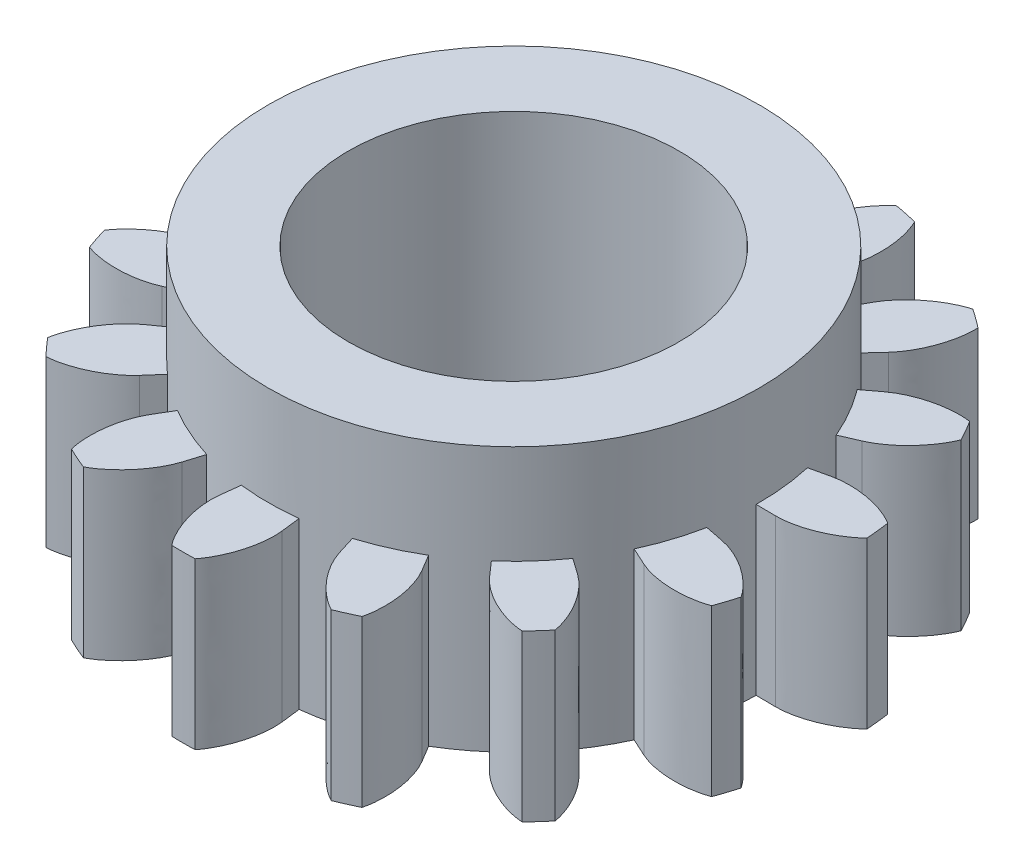
SolidWorks part; units mm, degrees
ref_plane "Front Plane" through (0, 0, 0) normal (0, 0, 1) x (1, 0, 0)
ref_plane "Top Plane" through (0, 0, 0) normal (0, 1, 0) x (1, 0, 0)
ref_plane "Right Plane" through (0, 0, 0) normal (1, 0, 0) x (0, 0, -1)
sketch "Sketch1" plane through (0, 0, 0) normal (0, 1, 0) x (1, 0, 0)
  line L0 (-8.7707, -0.0085) -> (8.7293, -0.0085) construction
  dimension "D1" = 17.5
sketch "Sketch2" plane through (0, 0, 0) normal (0, 1, 0) x (1, 0, 0)
  line L0 (-2.583, 7.5851) -> (-2.3919, 7.0239)
  line L1 (-0.7409, 7.9785) -> (-0.6861, 7.3882)
  line L2 (0, 0) -> (-2.6402, 12.3623) construction
  line L3 (2.5683, 7.5901) -> (2.3783, 7.0285)
  line L4 (0.7255, 7.9799) -> (0.6718, 7.3895)
  line L5 (5.4334, 5.8892) -> (5.0314, 5.4536)
  line L6 (3.9085, 6.9949) -> (3.6193, 6.4774)
  line L7 (7.359, 3.1701) -> (6.8146, 2.9356)
  line L8 (6.4157, 4.8005) -> (5.941, 4.4453)
  line L9 (8.0122, -0.0971) -> (7.4195, -0.0899)
  line L10 (7.8135, 1.776) -> (7.2355, 1.6446)
  line L11 (7.28, -3.3476) -> (6.7414, -3.0999)
  line L12 (7.8604, -1.5556) -> (7.2788, -1.4405)
  line L13 (5.289, -6.0192) -> (4.8977, -5.5739)
  line L14 (6.5481, -4.6182) -> (6.0636, -4.2766)
  line L15 (2.3835, -7.6501) -> (2.2072, -7.0841)
  line L16 (4.1036, -6.8823) -> (3.8, -6.3731)
  line L17 (-0.9341, -7.9582) -> (-0.865, -7.3694)
  line L18 (0.9495, -7.9564) -> (0.8793, -7.3677)
  line L19 (-4.0902, -6.8902) -> (-3.7876, -6.3805)
  line L20 (-2.3687, -7.6547) -> (-2.1935, -7.0884)
  line L21 (-6.5391, -4.6309) -> (-6.0553, -4.2883)
  line L22 (-5.2774, -6.0295) -> (-4.887, -5.5834)
  line L23 (-7.8573, -1.5708) -> (-7.276, -1.4546)
  line L24 (-7.2735, -3.3617) -> (-6.7354, -3.113)
  line L25 (-7.8169, 1.7608) -> (-7.2386, 1.6306)
  line L26 (-8.012, -0.1126) -> (-7.4193, -0.1043)
  line L27 (-6.4249, 4.788) -> (-5.9496, 4.4338)
  line L28 (-7.3652, 3.1559) -> (-6.8203, 2.9224)
  line L29 (-3.922, 6.9874) -> (-3.6318, 6.4704)
  line L30 (-5.4448, 5.8787) -> (-5.042, 5.4438)
  circle A0 centre (0, 0) radius 8.75 construction
  arc A1 (-1.7416, 9.8472) -> (-2.433, 9.6995) centre (0, 0) ccw
  circle A2 centre (0, 0) radius 7.42
  arc A3 (2.4142, 9.7042) -> (1.7225, 9.8505) centre (0, 0) ccw
  circle A4 centre (0, 0) radius 8.0128 construction
  arc A5 (6.1525, 7.8833) -> (5.5802, 8.2983) centre (0, 0) ccw
  arc A6 (8.827, 4.6993) -> (8.473, 5.3112) centre (0, 0) ccw
  arc A7 (9.9753, 0.7027) -> (9.9007, 1.4058) centre (0, 0) ccw
  arc A8 (9.3987, -3.4153) -> (9.6165, -2.7428) centre (0, 0) ccw
  arc A9 (7.197, -6.9429) -> (7.6695, -6.417) centre (0, 0) ccw
  arc A10 (3.7509, -9.2699) -> (4.3964, -8.9817) centre (0, 0) ccw
  arc A11 (-0.3438, -9.9941) -> (0.3632, -9.9934) centre (0, 0) ccw
  arc A12 (-4.3791, -8.9902) -> (-3.7329, -9.2771) centre (0, 0) ccw
  arc A13 (-7.6571, -6.4318) -> (-7.1835, -6.9568) centre (0, 0) ccw
  arc A14 (-9.6112, -2.7614) -> (-9.3921, -3.4335) centre (0, 0) ccw
  arc A15 (-9.9034, 1.3866) -> (-9.9766, 0.6834) centre (0, 0) ccw
  arc A16 (-8.4832, 5.2948) -> (-8.8361, 4.6822) centre (0, 0) ccw
  arc A17 (-5.5962, 8.2875) -> (-6.1678, 7.8714) centre (0, 0) ccw
  spline S0 degree 3 poles (-2.583, 7.5851) (-2.7933, 8.2026) (-2.7279, 9.0974) (-2.433, 9.6995) knots 0 0 0 0 1 1 1 1
  spline S1 degree 3 poles (-0.7409, 7.9785) (-0.8012, 8.6281) (-1.2264, 9.4181) (-1.7416, 9.8472) knots 0 0 0 0 1 1 1 1
  spline S2 degree 3 poles (2.5683, 7.5901) (2.7774, 8.208) (2.7103, 9.1027) (2.4142, 9.7042) knots 0 0 0 0 1 1 1 1
  spline S3 degree 3 poles (0.7255, 7.9799) (0.7845, 8.6296) (1.2082, 9.4205) (1.7225, 9.8505) knots 0 0 0 0 1 1 1 1
  spline S4 degree 3 poles (5.4334, 5.8892) (5.8758, 6.3687) (6.1784, 7.2134) (6.1525, 7.8833) knots 0 0 0 0 1 1 1 1
  spline S5 degree 3 poles (3.9085, 6.9949) (4.2267, 7.5644) (4.9354, 8.1146) (5.5802, 8.2983) knots 0 0 0 0 1 1 1 1
  spline S6 degree 3 poles (7.359, 3.1701) (7.9582, 3.4282) (8.5782, 4.0768) (8.827, 4.6993) knots 0 0 0 0 1 1 1 1
  spline S7 degree 3 poles (6.4157, 4.8005) (6.938, 5.1913) (7.8092, 5.4056) (8.473, 5.3112) knots 0 0 0 0 1 1 1 1
  spline S8 degree 3 poles (8.0122, -0.0971) (8.6646, -0.105) (9.4947, 0.2353) (9.9753, 0.7027) knots 0 0 0 0 1 1 1 1
  spline S9 degree 3 poles (7.8135, 1.776) (8.4497, 1.9206) (9.3327, 1.762) (9.9007, 1.4058) knots 0 0 0 0 1 1 1 1
  spline S10 degree 3 poles (7.28, -3.3476) (7.8727, -3.6202) (8.7695, -3.6469) (9.3987, -3.4153) knots 0 0 0 0 1 1 1 1
  spline S11 degree 3 poles (7.8604, -1.5556) (8.5003, -1.6823) (9.2426, -2.1863) (9.6165, -2.7428) knots 0 0 0 0 1 1 1 1
  spline S12 degree 3 poles (5.289, -6.0192) (5.7197, -6.5093) (6.528, -6.8985) (7.197, -6.9429) knots 0 0 0 0 1 1 1 1
  spline S13 degree 3 poles (6.5481, -4.6182) (7.0812, -4.9942) (7.5542, -5.7566) (7.6695, -6.417) knots 0 0 0 0 1 1 1 1
  spline S14 degree 3 poles (2.3835, -7.6501) (2.5776, -8.2729) (3.1578, -8.9573) (3.7509, -9.2699) knots 0 0 0 0 1 1 1 1
  spline S15 degree 3 poles (4.1036, -6.8823) (4.4377, -7.4426) (4.5597, -8.3315) (4.3964, -8.9817) knots 0 0 0 0 1 1 1 1
  spline S16 degree 3 poles (-0.9341, -7.9582) (-1.0102, -8.6061) (-0.7585, -9.4673) (-0.3438, -9.9941) knots 0 0 0 0 1 1 1 1
  spline S17 degree 3 poles (0.9495, -7.9564) (1.0268, -8.6041) (0.7768, -9.4658) (0.3632, -9.9934) knots 0 0 0 0 1 1 1 1
  spline S18 degree 3 poles (-4.0902, -6.8902) (-4.4232, -7.4512) (-4.5436, -8.3403) (-4.3791, -8.9902) knots 0 0 0 0 1 1 1 1
  spline S19 degree 3 poles (-2.3687, -7.6547) (-2.5616, -8.2779) (-3.1404, -8.9634) (-3.7329, -9.2771) knots 0 0 0 0 1 1 1 1
  spline S20 degree 3 poles (-6.5391, -4.6309) (-7.0715, -5.0079) (-7.5431, -5.7712) (-7.6571, -6.4318) knots 0 0 0 0 1 1 1 1
  spline S21 degree 3 poles (-5.2774, -6.0295) (-5.7071, -6.5204) (-6.5147, -6.9111) (-7.1835, -6.9568) knots 0 0 0 0 1 1 1 1
  spline S22 degree 3 poles (-7.8573, -1.5708) (-8.4971, -1.6987) (-9.2383, -2.2042) (-9.6112, -2.7614) knots 0 0 0 0 1 1 1 1
  spline S23 degree 3 poles (-7.2735, -3.3617) (-7.8657, -3.6354) (-8.7625, -3.6639) (-9.3921, -3.4335) knots 0 0 0 0 1 1 1 1
  spline S24 degree 3 poles (-7.8169, 1.7608) (-8.4534, 1.9042) (-9.3361, 1.7439) (-9.9034, 1.3866) knots 0 0 0 0 1 1 1 1
  spline S25 degree 3 poles (-8.012, -0.1126) (-8.6643, -0.1218) (-9.4951, 0.2169) (-9.9766, 0.6834) knots 0 0 0 0 1 1 1 1
  spline S26 degree 3 poles (-6.4249, 4.788) (-6.948, 5.1779) (-7.8197, 5.3905) (-8.4832, 5.2948) knots 0 0 0 0 1 1 1 1
  spline S27 degree 3 poles (-7.3652, 3.1559) (-7.9648, 3.4128) (-8.586, 4.0602) (-8.8361, 4.6822) knots 0 0 0 0 1 1 1 1
  spline S28 degree 3 poles (-3.922, 6.9874) (-4.2413, 7.5563) (-4.9511, 8.105) (-5.5962, 8.2875) knots 0 0 0 0 1 1 1 1
  spline S29 degree 3 poles (-5.4448, 5.8787) (-5.8881, 6.3574) (-6.1923, 7.2014) (-6.1678, 7.8714) knots 0 0 0 0 1 1 1 1
  point P129 (0, 0)
  dimension "D1" = 17.5
  dimension "D2" = 20
  dimension "D3" = 6.75
  dimension "D4" = 15
extrude "Boss-Extrude1" add sketch "Sketch2" along normal blind 5 contours A2 | S21 L22 A2 L21 S20 A13 | S19 L20 A2 L19 S18 A12 | S17 L18 A2 L17 S16 A11 | S15 L16 A2 L15 S14 A10 | S13 L14 A2 L13 S12 A9 | S11 L12 A2 L11 S10 A8 | S9 L10 A2 L9 S8 A7 | S7 L8 A2 L7 S6 A6 | S5 L6 A2 L5 S4 A5 | S3 L4 A2 L3 S2 A3 | L1 S1 A1 S0 L0 A2 | S29 L30 A2 L29 S28 A17 | S27 L28 A2 L27 S26 A16 | S25 L26 A2 L25 S24 A15 | S23 L24 A2 L23 S22 A14 region at (-1.7902, 0, -8.3824) region at (0, 0, 0) region at (-5.0448, 0, -6.9295) region at (1.774, 0, -8.3858) region at (-7.4272, 0, -4.2785) region at (5.0314, 0, -6.9393) region at (-8.5253, 0, -0.8877) region at (7.4189, 0, -4.2929) region at (-8.1493, 0, 2.6566) region at (8.5236, 0, -0.9042) region at (-6.3642, 0, 5.7415) region at (8.1544, 0, 2.6408) region at (-3.4787, 0, 7.8337) region at (6.3753, 0, 5.7292) region at (0.0083, 0, 8.5714) region at (3.4939, 0, 7.827)
sketch "Sketch3" plane through (0, 0, 0) normal (0, 1, 0) x (1, 0, 0)
  line L0 (-0.9341, -7.9582) -> (-0.865, -7.3694) construction
  line L1 (0.9495, -7.9564) -> (0.8793, -7.3677) construction
  line L2 (-0.9341, -7.9582) -> (-0.865, -7.3694)
  line L3 (0.9495, -7.9564) -> (0.8793, -7.3677)
  arc A0 (-0.3438, -9.9941) -> (0.3632, -9.9934) centre (0, 0) ccw construction
  arc A1 (-0.3438, -9.9941) -> (0.3632, -9.9934) centre (0, 0) ccw
  spline S0 degree 3 poles (-737.2821, -1866.0649) (639.9603, 1925.5089) (-525.9262, -1977.2204) (401.7888, 1948.6545) knots -14.720502 -14.720502 -14.720502 -14.720502 15.764896 15.764896 15.764896 15.764896 only from (0.9495, -7.9564) to (0.3632, -9.9934) construction
  spline S1 degree 3 poles (740.8911, -1864.635) (-643.6846, 1924.2671) (529.7507, -1976.1991) (-405.5583, 1947.8735) knots -14.720502 -14.720502 -14.720502 -14.720502 15.764896 15.764896 15.764896 15.764896 only from (-0.9341, -7.9582) to (-0.3438, -9.9941) construction
  spline S2 degree 3 poles (0.9495, -7.9564) (1.0268, -8.6041) (0.7768, -9.4658) (0.3632, -9.9934) knots 0 0 0 0 1 1 1 1
  spline S3 degree 3 poles (-0.9341, -7.9582) (-1.0102, -8.6061) (-0.7585, -9.4673) (-0.3438, -9.9941) knots 0 0 0 0 1 1 1 1
sketch "Sketch4" plane through (0, 5, 0) normal (0, 1, 0) x (1, 0, 0)
  circle A0 centre (0, 0) radius 2.5
  dimension "D1" = 5
extrude "Cut-Extrude1" cut sketch "Sketch4" against normal through all both
sketch "Sketch5" plane through (0, 5, 0) normal (0, 1, 0) x (1, 0, 0)
  circle A1 centre (0, 0) radius 2.5
  circle A2 centre (0, 0) radius 5
  circle A3 centre (0, 0) radius 7.42
  dimension "D1" = 10
extrude "Cut-Extrude2" cut sketch "Sketch5" against normal up to surface (5 mm away) contours A2 A1 region at (-4.8586, 5, 0) up to face at (0, 0, 2.5)
extrude "Boss-Extrude2" add sketch "Sketch5<3>" along normal blind 8 from surface contours A3 A2 region at (-7.2101, 5, 0) starting at face at (0, 0, 5)
sketch "Sketch5<3>" plane through (0, 5, 0) normal (0, 1, 0) x (1, 0, 0) same geometry as "Sketch5"
